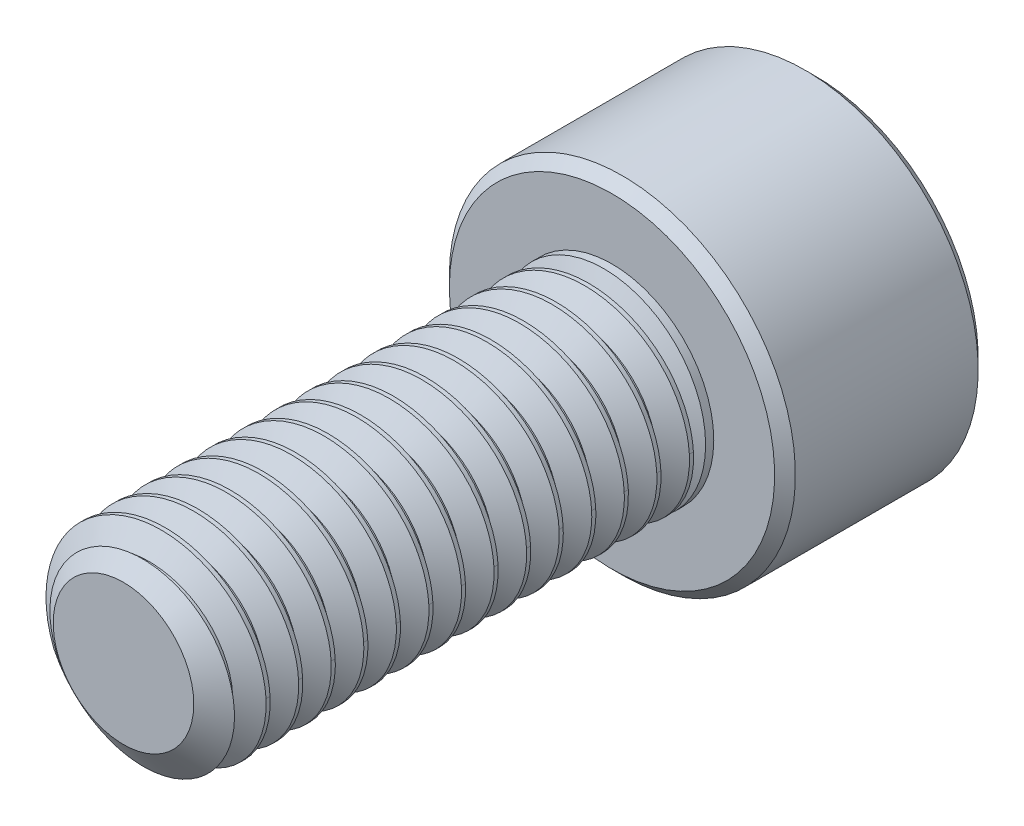
SolidWorks part; units mm, degrees
ref_plane "Front Plane" through (0, 0, 0) normal (0, 0, 1) x (1, 0, 0)
ref_plane "Top Plane" through (0, 0, 0) normal (0, 1, 0) x (1, 0, 0)
ref_plane "Right Plane" through (0, 0, 0) normal (1, 0, 0) x (0, 0, -1)
sketch "Sketch1" plane through (0, 0, 0) normal (0, 0, 1) x (1, 0, 0)
  circle A0 centre (0, 0) radius 2.5
  dimension "OD" = 5
extrude "Extrude1" add sketch "Sketch1" against normal blind 12
sketch "Sketch2" plane through (0, 0, 0) normal (0, 0, 1) x (1, 0, 0)
  circle A0 centre (0, 0) radius 2.5 construction
  circle A1 centre (0, 0) radius 2.5
curve "Helix/Spiral1" pitch 0.8 height 12.8 turns 16 parameters "pitch"=0.8
sketch "Sketch3" plane through (0, 0, 0) normal (1, 0, 0) x (0, 0, -1)
  line L0 (-0.7, 2.5) -> (-0.4, 1.9804)
  line L1 (-0.4, 1.9804) -> (-0.3, 1.9804)
  line L2 (-0.3, 1.9804) -> (0, 2.5)
  line L3 (-0.7, 2.5) -> (0, 2.5)
  line L4 (-0.35, 2.5) -> (-0.35, 1.9804) construction
  line L5 (-0.55, 2.2402) -> (-0.15, 2.2402) construction
  line L6 (0, 2.5) -> (0, -2.5) construction
  line L7 (0, -2.5) -> (12, -2.5) construction
  point P11 (3.6, -2.5)
  dimension "D1" = 0.1
  dimension "D2" = 0.4
  dimension "D3" = 60
  dimension "D4" = 3.6
sweep "Cut-Sweep1" cut profiles "Sketch3" path "Helix/Spiral1"
sketch "Sketch4" plane through (0, 0, 0) normal (1, 0, 0) x (0, 0, -1)
  line L0 (0.5417, 2.5) -> (0, 1.7264)
  line L1 (0, 1.7264) -> (0, 2.5)
  line L2 (0.5417, 2.5) -> (0, 2.5)
  line L3 (-0.7, 2.5) -> (0, 2.5) construction
  line L4 (0, 0) -> (7.0209, 0) construction
  dimension "D1" = 55
  dimension "D2" = 0.254
revolve "Cut-Revolve1" cut sketch "Sketch4" angle 360 about L4
sketch "Sketch5" plane through (0, 0, 0) normal (1, 0, 0) x (0, 0, -1)
  line L0 (12, -1.991) -> (12, 1.7838) construction
  line L1 (12, 2.5) -> (0.1203, 2.5)
  line L2 (12, 2.5) -> (12, 0)
  line L3 (12, 0) -> (0.0001, 0)
  line L4 (0.0001, 2.1698) -> (0.0001, 0)
  line L5 (0.1203, 2.5) -> (0.0001, 2.1698)
  line L6 (0, 0) -> (9.9695, 0) construction
  point P3 (0.0001, 2.5)
  point P10 (0.0001, 2.5)
  dimension "D1" = 0.3302
  dimension "Thread min" = 0.0001
  dimension "D3" = 20
revolve "partially thread" [suppressed] add sketch "Sketch5" angle 360 about L6
sketch "Sketch6" plane through (0, 0, -12) normal (0, 0, -1) x (-1, 0, 0)
  circle A0 centre (0, 0) radius 4.25
  dimension "head dia" = 8.5
extrude "Extrude2" add sketch "Sketch6" along normal blind 5
sketch "Sketch7" plane through (0, 0, -17) normal (0, 0, -1) x (-1, 0, 0)
  line L1 (0, 2.3094) -> (-2, 1.1547)
  line L2 (-2, 1.1547) -> (-2, -1.1547)
  line L3 (-2, -1.1547) -> (0, -2.3094)
  line L4 (0, -2.3094) -> (2, -1.1547)
  line L5 (2, -1.1547) -> (2, 1.1547)
  line L6 (2, 1.1547) -> (0, 2.3094)
  circle A0 centre (0, 0) radius 2 construction
  dimension "hex dia" = 4
extrude "Cut-Extrude1" cut sketch "Sketch7" against normal blind 3
sketch "Sketch8" plane through (0, 0, -17) normal (0, 0, -1) x (-1, 0, 0)
  circle A0 centre (0, 0) radius 2.3094
extrude "Cut-Extrude2" cut sketch "Sketch8" against normal through all draft 45
chamfer "Chamfer1" distance 0.255 angle 45 2 edges at (-4.25, 0, -17) (-4.25, 0, -12)
sketch "Sketch9" plane through (0, 0, 0) normal (1, 0, 0) x (0, 0, -1)
  line L0 (0, 2.5) -> (0, -2.5) construction
  line L1 (4.4, 2.5) -> (4.4, -2.5) construction
  dimension "D1" = 4.4
sketch "Sketch10" plane through (0, 0, 0) normal (1, 0, 0) x (0, 0, -1)
  line L0 (12, 2.5) -> (12, 0)
  line L1 (12, 2.5) -> (11.8, 2.5)
  line L2 (11.8, 2.5) -> (10.7645, 0)
  line L3 (12, 0) -> (10.7645, 0)
  line L4 (12, 3.995) -> (12, -3.995) construction
  dimension "D1" = 22.5
  dimension "D2" = 0.2
revolve "Revolve1" add sketch "Sketch10" angle 360 about L3
equation "\"D3@Helix/Spiral1\" = \"screw length@Extrude1\"+\"pitch@Helix/Spiral1\""
equation "\"D1@Sketch3\" = \"pitch@Helix/Spiral1\"*.125"
equation "\"D2@Sketch3\" = \"pitch@Helix/Spiral1\"*.5"
equation "\"D1@Cut-Extrude1\" = \"hex dia@Sketch7\"*.75"
equation "\"D1@Chamfer1\" = \"head dia@Sketch6\"*.03"
equation "\"D1@Sketch9\" = \"pitch@Helix/Spiral1\"*5.5"
equation "\"D2@Sketch10\" = \"pitch@Helix/Spiral1\"*.25"
equation "\"D4@Sketch3\" = \"pitch@Helix/Spiral1\"*4.50"
